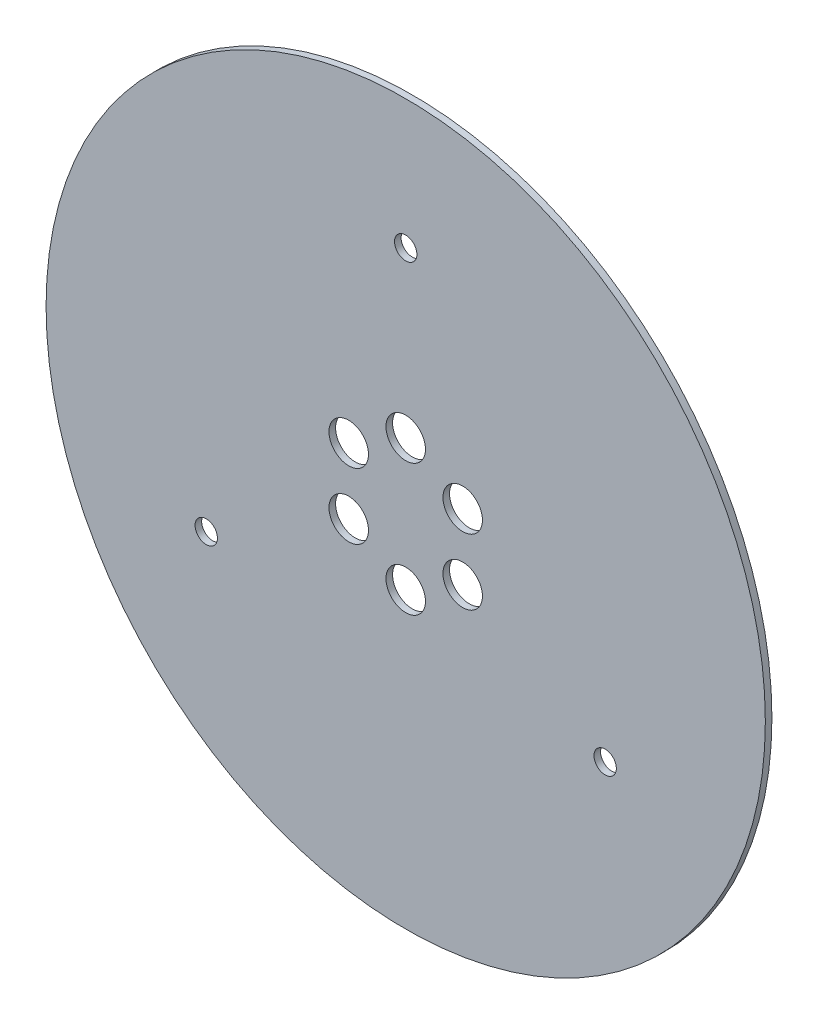
SolidWorks part; units mm, degrees
material "PETG"
ref_plane "Front Plane" through (0, 0, 0) normal (0, 0, 1) x (1, 0, 0)
ref_plane "Top Plane" through (0, 0, 0) normal (0, 1, 0) x (1, 0, 0)
ref_plane "Right Plane" through (0, 0, 0) normal (1, 0, 0) x (0, 0, -1)
sketch "Sketch1" plane through (0, 0, 0) normal (0, 0, 1) x (1, 0, 0)
  line L0 (0, 0) -> (0, 35) construction
  line L1 (0, 0) -> (0, 10) construction
  circle A0 centre (0, 0) radius 54.6563
  circle A1 centre (0, 35) radius 1.7
  circle A2 centre (30.3109, -17.5) radius 1.7
  circle A3 centre (-30.3109, -17.5) radius 1.7
  circle A4 centre (0, 10) radius 3
  circle A5 centre (8.6603, 5) radius 3
  circle A6 centre (8.6603, -5) radius 3
  circle A7 centre (0, -10) radius 3
  circle A8 centre (-8.6603, -5) radius 3
  circle A9 centre (-8.6603, 5) radius 3
  point P11 (0, 0)
  dimension "D1" = 109.3127
  dimension "D2" = 3.4
  dimension "D4" = 6
  dimension "D7" = 35
  dimension "D5" = 10
  dimension "D6" = 3
  dimension "D3" = 6
extrude "Boss-Extrude1" add sketch "Sketch1" along normal blind 1
equation "\"tol_dia_id_intfc\" = 0.0200mm ' For hole diameters - Interference fit"
equation "\"tol_dia_id_slip\"  = 0.0300mm ' For hole diameters - Slip fit"
equation "\"tol_dia_id_clear\" = 0.0500mm ' For hole diameters - Clearance fit"
equation "\"tol_dia_od_intfc\" = 0.0200mm ' For shaft diameters - Interference fit"
equation "\"tol_dia_od_slip\"  = 0.0300mm ' For shaft diameters - Slip fit"
equation "\"tol_dia_od_clear\" = 0.0500mm ' For shaft diameters - Clearance fit"
equation "\"tol_general_intfc\"= 0.0030mm ' For general parts (Horiz) - Interference fit"
equation "\"tol_general_slip\" = 0.0050mm ' For general parts (Horiz) - Slip fit"
equation "\"tol_general_clear\"= 0.0100mm ' For general parts (Horiz) - Clearance fit"
equation "\"tol_layer_intfc\"  = 0.0030mm ' For all parts (Vert) - Interference fit"
equation "\"tol_layer_slip\"   = 0.0050mm ' For all parts (Vert) - Slip fit"
equation "\"tol_layer_clear\"  = 0.0100mm ' For all parts (Vert) - Clearance fit"
equation "\"tol_corner_rad\"   = 0.100mm ' For corners that fit into other parts"
equation "\"pitch\"= 8mm"
equation "\"n\"= 39"
equation "\"pitch_dia\"= \"pitch\" * \"n\" / PI"
equation "\"belt_width\"= 22mm"
equation "\"D1@Sketch1\"=\"pitch_dia\"+10"
